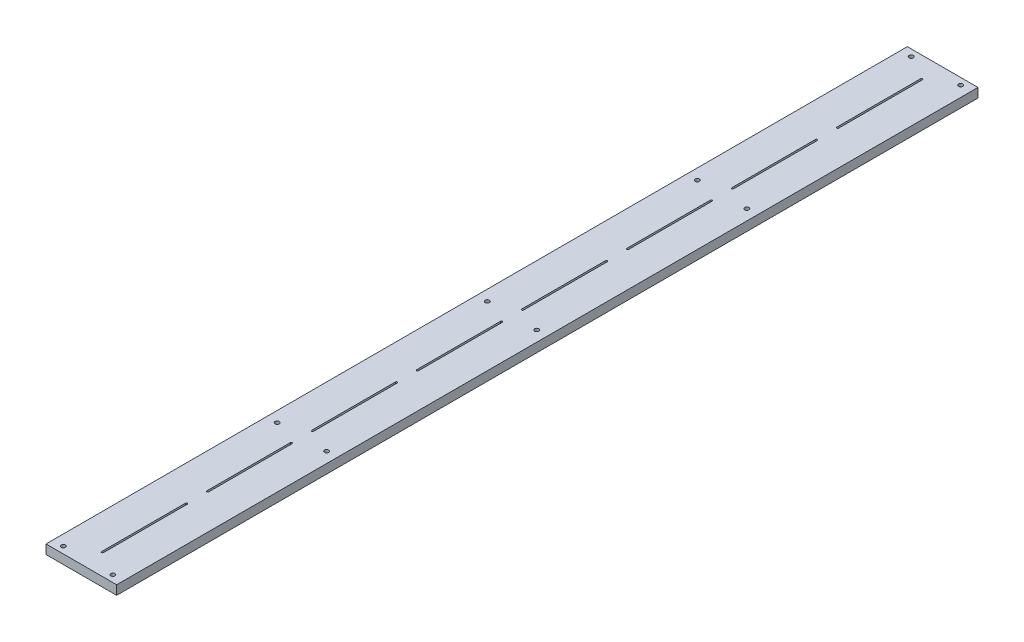
SolidWorks part; units mm, degrees
ref_plane "Front Plane" through (0, 0, 0) normal (0, 0, 1) x (1, 0, 0)
ref_plane "Top Plane" through (0, 0, 0) normal (0, 1, 0) x (1, 0, 0)
ref_plane "Right Plane" through (0, 0, 0) normal (1, 0, 0) x (0, 0, -1)
sketch "Sketch1" plane through (0, 0, 0) normal (0, 1, 0) x (1, 0, 0)
  line L1 (-50, 609.6) -> (50, 609.6)
  line L2 (-50, 609.6) -> (-50, -609.6)
  line L3 (-50, -609.6) -> (50, -609.6)
  line L4 (50, 609.6) -> (50, -609.6)
  line L5 (-50, 609.6) -> (50, -609.6) construction
  line L6 (-50, -609.6) -> (50, 609.6) construction
  point P0 (0, 0)
  dimension "D1" = 1219.2
  dimension "D2" = 100
extrude "Boss-Extrude1" add sketch "Sketch1" along normal blind 13
sketch "Sketch5" plane through (0, 13, 0) normal (0, 1, 0) x (1, 0, 0)
  line L0 (50, -609.6) -> (50, 609.6) construction
  line L1 (-50, -450.95) -> (50, -450.95)
  line L2 (-50, -450.95) -> (-50, -589.6)
  line L3 (-50, -589.6) -> (50, -589.6)
  line L4 (50, -450.95) -> (50, -589.6)
  line L5 (-50, 609.6) -> (-50, -609.6) construction
  line L6 (-50, -302.3) -> (50, -302.3)
  line L7 (-50, -302.3) -> (-50, -440.95)
  line L8 (-50, -440.95) -> (50, -440.95)
  line L9 (50, -302.3) -> (50, -440.95)
  line L10 (-50, -153.65) -> (50, -153.65)
  line L11 (-50, -153.65) -> (-50, -292.3)
  line L12 (-50, -292.3) -> (50, -292.3)
  line L13 (50, -153.65) -> (50, -292.3)
  line L14 (-50, -5) -> (50, -5)
  line L15 (-50, -5) -> (-50, -143.65)
  line L16 (-50, -143.65) -> (50, -143.65)
  line L17 (50, -5) -> (50, -143.65)
  line L18 (-50, 143.65) -> (50, 143.65)
  line L19 (-50, 143.65) -> (-50, 5)
  line L20 (-50, 5) -> (50, 5)
  line L21 (50, 143.65) -> (50, 5)
  line L22 (-50, 292.3) -> (50, 292.3)
  line L23 (-50, 292.3) -> (-50, 153.65)
  line L24 (-50, 153.65) -> (50, 153.65)
  line L25 (50, 292.3) -> (50, 153.65)
  line L26 (-50, 440.95) -> (50, 440.95)
  line L27 (-50, 440.95) -> (-50, 302.3)
  line L28 (-50, 302.3) -> (50, 302.3)
  line L29 (50, 440.95) -> (50, 302.3)
  line L30 (-50, 589.6) -> (50, 589.6)
  line L31 (-50, 589.6) -> (-50, 450.95)
  line L32 (-50, 450.95) -> (50, 450.95)
  line L33 (50, 589.6) -> (50, 450.95)
  line L34 (-50, -609.6) -> (50, -609.6) construction
  line L35 (50, 609.6) -> (-50, 609.6) construction
  dimension "D1" = 20
  dimension "D3" = 20
  dimension "D4" = 10
  dimension "D2" = 8
sketch "Sketch6" plane through (0, 13, 0) normal (0, 1, 0) x (1, 0, 0)
  line L2 (-50, 302.3) -> (50, 302.3) construction
  line L3 (50, 292.3) -> (50, 153.65) construction
  line L4 (0, 0) -> (-79.7583, 0) construction
  line L5 (50, 609.6) -> (-50, 609.6) construction
  line L6 (50, -609.6) -> (50, 609.6) construction
  circle A0 centre (35, 0) radius 3
  circle A1 centre (-35, 0) radius 3
  circle A2 centre (35, -297.3) radius 3
  circle A3 centre (-35, -297.3) radius 3
  circle A4 centre (35, 600.1) radius 3
  circle A5 centre (-35, 600.1) radius 3
  circle A6 centre (-35, 297.3) radius 3
  circle A7 centre (35, 297.3) radius 3
  circle A8 centre (-35, 594.6) radius 3 [skipped]
  circle A9 centre (35, 594.6) radius 3 [skipped]
  circle A10 centre (-35, -600.1) radius 3
  circle A11 centre (35, -600.1) radius 3
  dimension "D1" = 6
  dimension "D2" = 35
  dimension "D6" = 15
  dimension "D8" = 9.5
  dimension "D3" = 35
  dimension "D5" = 5
  dimension "D9" = 15
  dimension "D4" = 2
  dimension "D7" = 2
extrude "Cut-Extrude4" cut sketch "Sketch6" against normal blind 20
sketch "Sketch7" plane through (0, 13, 0) normal (0, 1, 0) x (1, 0, 0)
  line L0 (0, -460.95) -> (0, -579.6) construction
  line L1 (1.3, -460.95) -> (1.3, -579.6)
  line L2 (-1.3, -460.95) -> (-1.3, -579.6)
  line L4 (-50, -589.6) -> (50, -589.6) construction
  line L5 (-50, -450.95) -> (50, -450.95) construction
  line L6 (0, -312.3) -> (0, -430.95) construction
  line L7 (1.3, -312.3) -> (1.3, -430.95)
  line L8 (-1.3, -312.3) -> (-1.3, -430.95)
  line L9 (0, -163.65) -> (0, -282.3) construction
  line L10 (1.3, -163.65) -> (1.3, -282.3)
  line L11 (-1.3, -163.65) -> (-1.3, -282.3)
  line L12 (0, -15) -> (0, -133.65) construction
  line L13 (1.3, -15) -> (1.3, -133.65)
  line L14 (-1.3, -15) -> (-1.3, -133.65)
  line L15 (0, 133.65) -> (0, 15) construction
  line L16 (1.3, 133.65) -> (1.3, 15)
  line L17 (-1.3, 133.65) -> (-1.3, 15)
  line L18 (0, 282.3) -> (0, 163.65) construction
  line L19 (1.3, 282.3) -> (1.3, 163.65)
  line L20 (-1.3, 282.3) -> (-1.3, 163.65)
  line L21 (0, 430.95) -> (0, 312.3) construction
  line L22 (1.3, 430.95) -> (1.3, 312.3)
  line L23 (-1.3, 430.95) -> (-1.3, 312.3)
  line L24 (0, 579.6) -> (0, 460.95) construction
  line L25 (1.3, 579.6) -> (1.3, 460.95)
  line L26 (-1.3, 579.6) -> (-1.3, 460.95)
  line L27 (-50, 589.6) -> (50, 589.6) construction
  arc A0 (1.3, -460.95) -> (-1.3, -460.95) centre (0, -460.95) ccw
  arc A1 (-1.3, -579.6) -> (1.3, -579.6) centre (0, -579.6) ccw
  arc A2 (1.3, -312.3) -> (-1.3, -312.3) centre (0, -312.3) ccw
  arc A3 (-1.3, -430.95) -> (1.3, -430.95) centre (0, -430.95) ccw
  arc A4 (1.3, -163.65) -> (-1.3, -163.65) centre (0, -163.65) ccw
  arc A5 (-1.3, -282.3) -> (1.3, -282.3) centre (0, -282.3) ccw
  arc A6 (1.3, -15) -> (-1.3, -15) centre (0, -15) ccw
  arc A7 (-1.3, -133.65) -> (1.3, -133.65) centre (0, -133.65) ccw
  arc A8 (1.3, 133.65) -> (-1.3, 133.65) centre (0, 133.65) ccw
  arc A9 (-1.3, 15) -> (1.3, 15) centre (0, 15) ccw
  arc A10 (1.3, 282.3) -> (-1.3, 282.3) centre (0, 282.3) ccw
  arc A11 (-1.3, 163.65) -> (1.3, 163.65) centre (0, 163.65) ccw
  arc A12 (1.3, 430.95) -> (-1.3, 430.95) centre (0, 430.95) ccw
  arc A13 (-1.3, 312.3) -> (1.3, 312.3) centre (0, 312.3) ccw
  arc A14 (1.3, 579.6) -> (-1.3, 579.6) centre (0, 579.6) ccw
  arc A15 (-1.3, 460.95) -> (1.3, 460.95) centre (0, 460.95) ccw
  point P2 (0, -520.275)
  point P15 (0, -371.625)
  point P22 (0, -222.975)
  point P29 (0, -74.325)
  point P36 (0, 74.325)
  point P43 (0, 222.975)
  point P50 (0, 371.625)
  point P57 (0, 520.275)
  dimension "D2" = 1.3
  dimension "D1" = 10
  dimension "D7" = 148.65
  dimension "D8" = 148.65
  dimension "D9" = 148.65
  dimension "D10" = 148.65
  dimension "D3" = 10
  dimension "D5" = 10
  dimension "D6" = 148.65
  dimension "D4" = 8
extrude "Cut-Extrude5" cut sketch "Sketch7" against normal blind 30
ref_axis "Axis1" through (0, 13, 699.8972) along (0, 0, -1)
